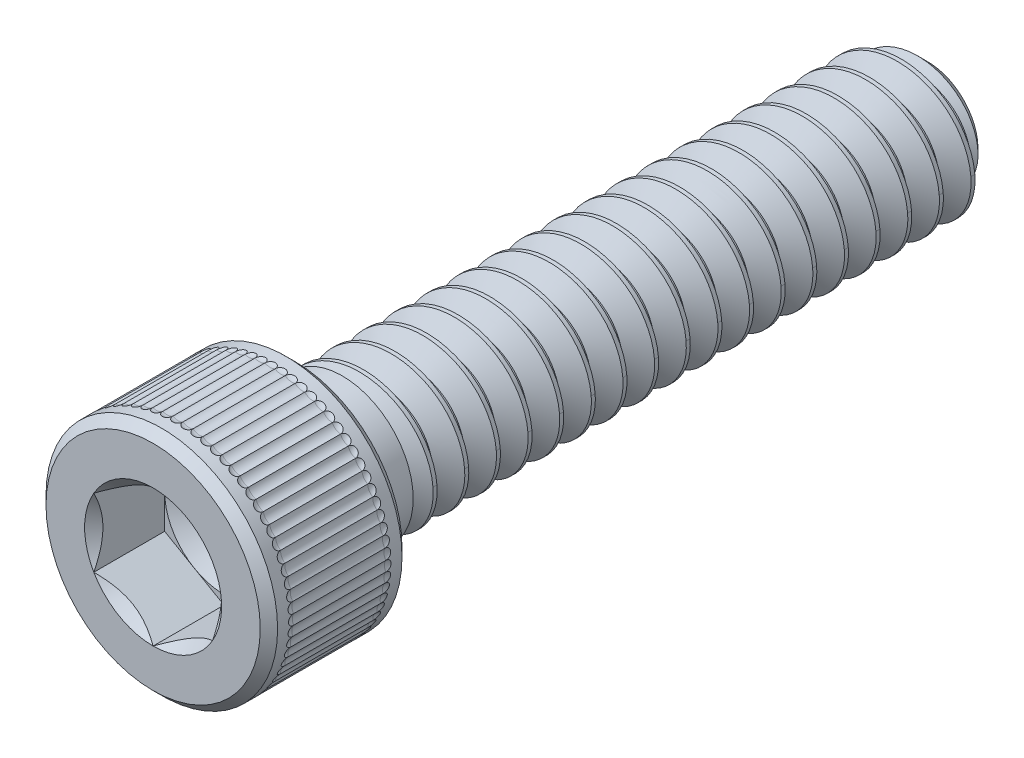
SolidWorks part; units mm, degrees
ref_plane "Front Plane" through (0, 0, 0) normal (0, 0, 1) x (1, 0, 0)
ref_plane "Top Plane" through (0, 0, 0) normal (0, 1, 0) x (1, 0, 0)
ref_plane "Right Plane" through (0, 0, 0) normal (1, 0, 0) x (0, 0, -1)
sketch "Sketch1" plane through (0, 0, 0) normal (1, 0, 0) x (0, 0, -1)
  line L0 (7.7724, 0) -> (-7.7724, 0) construction
  line L1 (-7.7724, -2.3241) -> (-7.7724, 2.3241) construction
  line L2 (-7.7724, 2.3241) -> (-4.9276, 2.3241) construction
  line L3 (7.7724, -1.4224) -> (7.7724, 1.4224) construction
  line L7 (7.7327, 1.4911) -> (8.3677, 1.4911) construction
  line L8 (8.3677, 1.4911) -> (8.0502, 0.9412) construction
  line L9 (8.0502, 0.9412) -> (7.7327, 1.4911) construction
  line L10 (8.0502, 1.4911) -> (8.0502, 1.4224) construction
  line L11 (8.0502, 1.4224) -> (8.0502, 1.01) construction
  line L12 (8.0502, 1.01) -> (8.0502, 0.9412) construction
  line L13 (8.0105, 1.01) -> (8.0899, 1.01) construction
  line L14 (7.7724, 1.4224) -> (8.328, 1.4224) construction
  line L15 (7.7526, 1.4568) -> (8.3479, 1.4568) construction
  line L17 (7.7724, -1.4224) -> (6.1849, -1.4224) construction
  point P4 (0, 0)
  point P8 (-7.7724, 0)
  point P11 (7.7724, 0)
  point P16 (-7.7724, 1.1906)
  point P20 (8.0502, 1.01)
  point P23 (8.0502, 1.4224)
  point P26 (8.0502, 1.4568)
  point P27 (-7.7724, -1.1906)
  dimension "Head Diameter" = 4.6482
  dimension "Head Height" = 2.8448
  dimension "Length" = 12.7
  dimension "Screw Size Decimal Equivalent" = 2.8448
  dimension "Thread Pitch" = 0.635
  dimension "D1" = 0.0794
  dimension "Drive Size" = 2.3813
  dimension "D2" = 1.5875
sketch "Sketch2" plane through (0, 0, 0) normal (1, 0, 0) x (0, 0, -1)
  line L0 (-5.1019, 2.3241) -> (-4.9276, 2.1498)
  line L1 (-7.7724, 2.3241) -> (-4.9276, 2.3241) construction
  line L2 (-7.7724, 1.1906) -> (-6.35, 1.1906)
  line L3 (-6.35, 1.1906) -> (-6.35, 0)
  line L4 (7.7724, 0) -> (-7.7724, 0) construction
  line L5 (-6.35, 0) -> (7.7724, 0)
  line L6 (7.7724, 0) -> (7.7724, 1.01)
  line L7 (7.7724, -1.4224) -> (7.7724, 1.4224) construction
  line L8 (7.7724, 1.01) -> (7.36, 1.4224)
  line L9 (7.36, 1.4224) -> (-4.7854, 1.4224)
  line L10 (-4.9276, 1.5646) -> (-4.9276, 2.1498)
  line L11 (-7.7724, 1.1906) -> (-7.7724, 2.1498)
  line L12 (-7.7724, -2.3241) -> (-7.7724, 2.3241) construction
  line L13 (-7.7724, 2.1498) -> (-7.5981, 2.3241)
  line L14 (-7.5981, 2.3241) -> (-5.1019, 2.3241)
  arc A0 (-4.7854, 1.4224) -> (-4.9276, 1.5646) centre (-4.7854, 1.5646) cw
  point P24 (-4.9276, 1.4224)
  dimension "D6" = 0.1422
  dimension "D1" = 45
  dimension "D3" = 1.4224
  dimension "D4" = 45
  dimension "D5" = 0.1743
  dimension "D2" = 0.1743
revolve "Revolve1" add sketch "Sketch2" angle 360 about L5
sketch "Sketch3" plane through (0, 0, 7.7724) normal (0, 0, 1) x (1, 0, 0)
  line L5 (0, 1.3748) -> (-1.1906, 0.6874)
  line L7 (-1.1906, 0.6874) -> (-1.1906, -0.6874)
  line L8 (-1.1906, -0.6874) -> (0, -1.3748)
  line L9 (0, -1.3748) -> (1.1906, -0.6874)
  line L10 (1.1906, -0.6874) -> (1.1906, 0.6874)
  line L11 (1.1906, 0.6874) -> (0, 1.3748)
  circle A1 centre (0, 0) radius 1.1906 construction
  circle A2 centre (0, 0) radius 1.1906 construction
extrude "Cut-Extrude1" cut sketch "Sketch3" against normal up to surface (1.4224 mm away) up to face at (1.1906, 0, 6.35)
sketch "Sketch4" plane through (0, 0, 7.7724) normal (0, 0, 1) x (1, 0, 0)
  circle A0 centre (0, 0) radius 1.3748
extrude "Cut-Extrude2" cut sketch "Sketch4" against normal through all draft 45
sketch "Sketch6" plane through (0, 0, 6.35) normal (0, 0, 1) x (1, 0, 0)
  line L0 (-1.1906, 0.6874) -> (-1.1906, -0.6874) construction
  circle A1 centre (0, 0) radius 1.1906
extrude "Cut-Extrude5" cut sketch "Sketch6" against normal through all draft 60
sketch "Sketch7" plane through (0, 0, -7.7724) normal (0, 0, -1) x (-1, 0, 0)
  circle A0 centre (0, 0) radius 1.4224
curve "Helix/Spiral1" pitch 0.635 height 13.0969 turns 20.625
sketch "Sketch8" plane through (0, 0, 0) normal (1, 0, 0) x (0, 0, -1)
  line L0 (7.7526, 1.4568) -> (8.3479, 1.4568)
  line L1 (8.3479, 1.4568) -> (8.0899, 1.01)
  line L2 (8.0899, 1.01) -> (8.0105, 1.01)
  line L3 (8.0105, 1.01) -> (7.7526, 1.4568)
sweep "Cut-Sweep1" cut profiles "Sketch8" path "Helix/Spiral1"
sketch "Sketch9" plane through (0, 0, 0) normal (1, 0, 0) x (0, 0, -1)
  line L0 (-5.3642, 0) -> (-5.3642, 1.5646)
  line L1 (7.7724, 0) -> (-7.7724, 0) construction
  line L2 (-4.7854, 1.4224) -> (-3.9751, 1.4224)
  line L3 (-3.9751, 1.4224) -> (-3.1539, 0)
  line L4 (-3.1539, 0) -> (-5.3642, 0)
  line L5 (7.7724, 1.4224) -> (8.328, 1.4224) construction
  line L8 (-6.35, 0) -> (7.7724, 0) construction
  line L9 (7.7724, 0) -> (7.7724, 1.01) construction
  line L10 (-5.3642, 1.5646) -> (-4.9276, 1.5646)
  arc A0 (-4.9276, 1.5646) -> (-4.7854, 1.4224) centre (-4.7854, 1.5646) ccw construction
  arc A1 (-4.9276, 1.5646) -> (-4.7854, 1.4224) centre (-4.7854, 1.5646) ccw
  dimension "D1" = 60
  dimension "D3" = 13.1366
  dimension "D2" = 0.9525
revolve "Revolve2" add sketch "Sketch9" angle 360 about L4
ref_plane "Plane1" through (0, 0, 6.35) normal (0, 0, -1) x (-1, 0, 0)
sketch "Sketch11" plane through (0, 0, 6.35) normal (0, 0, -1) x (-1, 0, 0)
  line L0 (0, 0) -> (0.1014, 2.3219) construction
  line L1 (0.1014, 2.3219) -> (-0.1014, 2.3219) construction
  line L2 (-0.1014, 2.3219) -> (0, 0) construction
  line L3 (0.1014, 2.3219) -> (0, 2.2634) construction
  line L4 (0, 2.2634) -> (-0.1014, 2.3219) construction
  circle A0 centre (0, 2.4975) radius 0.2028
  circle A1 centre (0, 0) radius 2.3241 construction
  dimension "D1" = 5
  dimension "D2" = 120
sketch "Sketch12" plane through (0, 0, 0) normal (1, 0, 0) x (0, 0, -1)
  line L0 (-7.2746, 2.2947) -> (-5.4254, 2.2947)
  line L1 (-7.4773, 2.4975) -> (-5.2227, 2.4975)
  arc A0 (-5.4254, 2.2947) -> (-5.2227, 2.4975) centre (-5.4254, 2.4975) ccw
  arc A1 (-7.2746, 2.2947) -> (-7.4773, 2.4975) centre (-7.2746, 2.4975) cw
  point P3 (-6.35, 2.4975)
  point P11 (-6.35, 2.2947)
  dimension "D1" = 1.8491
revolve "Cut-Revolve1" cut sketch "Sketch12" angle 360 about L1
pattern_circular "CirPattern1" count 72 over 360 about axis through (0, 0, 0) along (0, 0, 1) of "Cut-Revolve1"
equation "\"D1@Sketch1\"=\"Thread Pitch@Sketch1\"/8"
equation "\"D5@Sketch2\"=\"D2@Sketch2\""
equation "\"D3@Helix/Spiral1\"=\"Length@Sketch1\"+\"Thread Pitch@Sketch1\"*0.625"
equation "\"D4@Helix/Spiral1\"=\"Thread Pitch@Sketch1\""
equation "\"D2@Sketch2\"=\"Head Diameter@Sketch1\"*0.0375"
equation "\"D2@Sketch1\"=\"Thread Pitch@Sketch1\"*2.5"
equation "\"D3@Sketch2\"=\"Head Height@Sketch1\"*0.5"
equation "\"60g\"=45"
equation "\"D6@Sketch2\" = \"Screw Size Decimal Equivalent@Sketch1\" * 0.05"
equation "\"D3@Sketch9\"=\"D3@Helix/Spiral1\"+\"D1@Sketch1\"*0.5"
equation "\"D2@Sketch9\"=\"Thread Pitch@Sketch1\"*1.5"
equation "\"D1\"= \"Head Height@Sketch1\" * 0.075"
equation "\"D1@Sketch12\"=\"Head Height@Sketch1\"*.65"
equation "\"D1@CirPattern1\"=360/\"D1@Sketch11\""
